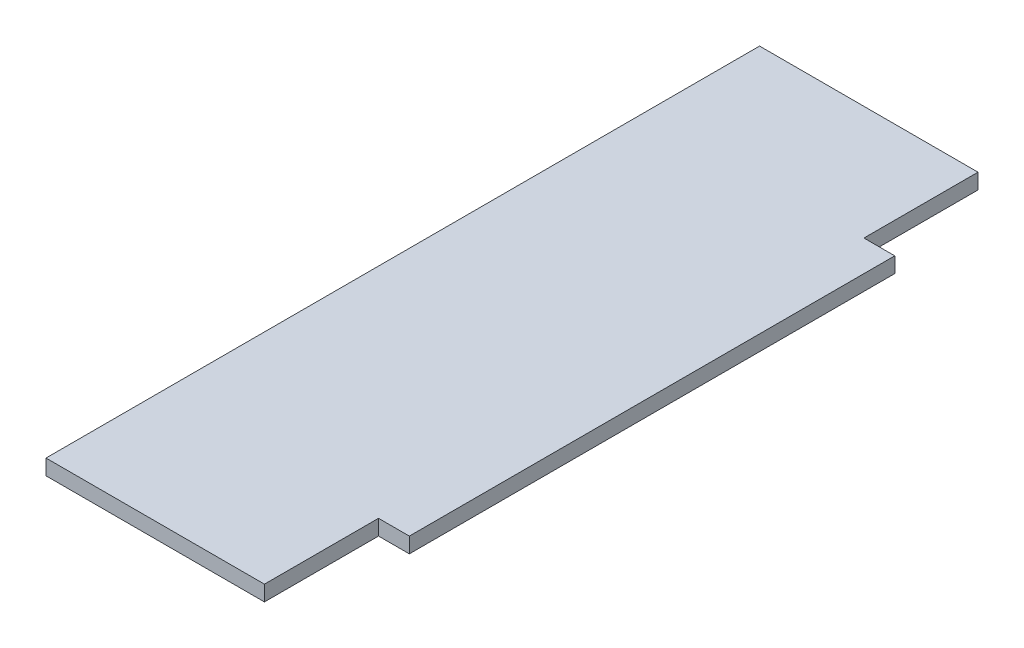
SolidWorks part; units mm, degrees
material "Cedar"
ref_plane "Front Plane" through (0, 0, 0) normal (0, 0, 1) x (1, 0, 0)
ref_plane "Top Plane" through (0, 0, 0) normal (0, 1, 0) x (1, 0, 0)
ref_plane "Right Plane" through (0, 0, 0) normal (1, 0, 0) x (0, 0, -1)
sketch "Sketch1" plane through (0, 0, 0) normal (0, 1, 0) x (1, 0, 0)
  line L0 (-22.5, 23.5) -> (22.5, 23.5)
  line L1 (22.5, 23.5) -> (22.5, 0)
  line L2 (22.5, 0) -> (28.85, 0)
  line L3 (28.85, 0) -> (28.85, -100)
  line L4 (28.85, -100) -> (22.5, -100)
  line L5 (22.5, -100) -> (22.5, -123.5)
  line L6 (22.5, -123.5) -> (-22.5, -123.5)
  line L7 (-22.5, -123.5) -> (-22.5, -100)
  line L8 (-22.5, -100) -> (-28.85, -100)
  line L9 (-28.85, -100) -> (-28.85, 0)
  line L10 (-28.85, 0) -> (-22.5, 0)
  line L11 (-22.5, 0) -> (-22.5, 23.5)
  line L12 (-22.5, 0) -> (-22.5, -100) construction
  point P11 (0, 23.5)
  point P14 (-28.85, -50)
  dimension "D1" = 6.35
  dimension "D2" = 100
  dimension "D3" = 45
  dimension "D4" = 147
extrude "Boss-Extrude1" add sketch "Sketch1" along normal blind 3.175 contours L11 L12 L7 L6 L5 L4 L3 L2 L1 L0 region at (2.2488, 0, 50)
equation "\"length\"= 147mm"
equation "\"w_mach\"= 45mm"
equation "\"w_tab\"= 100mm"
equation "\"t_wood\"= 0.125in"
equation "\"t_side\"= 0.25in"
equation "\"D1@Sketch1\"=\"t_side\""
equation "\"D2@Sketch1\"=\"w_tab\""
equation "\"D3@Sketch1\"=\"w_mach\""
equation "\"D4@Sketch1\"=\"length\""
equation "\"D1@Boss-Extrude1\"=\"t_wood\""
